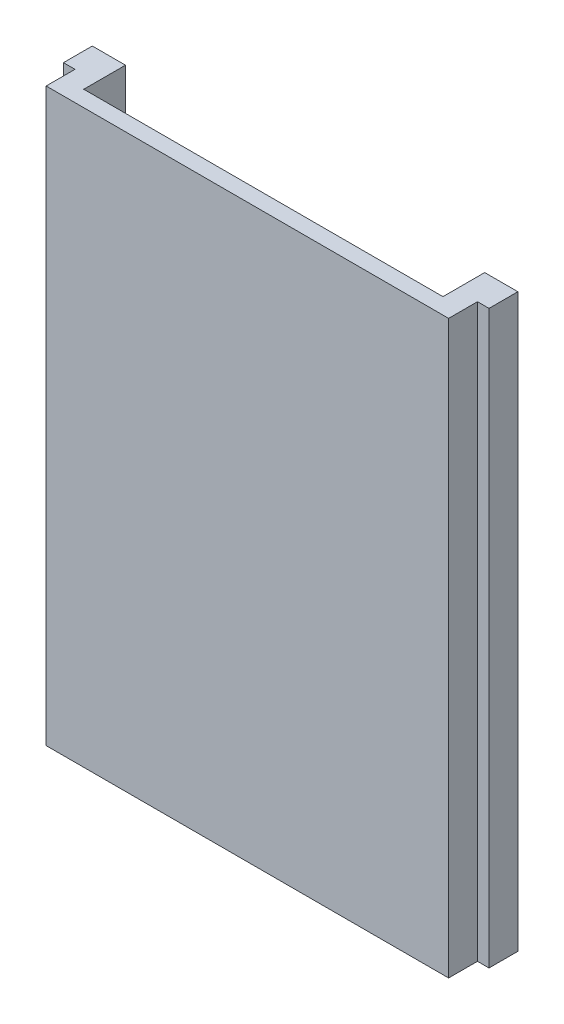
SolidWorks part; units mm, degrees
ref_plane "Alzado" through (0, 0, 0) normal (0, 0, 1) x (1, 0, 0)
ref_plane "Planta" through (0, 0, 0) normal (0, 1, 0) x (1, 0, 0)
ref_plane "Vista lateral" through (0, 0, 0) normal (1, 0, 0) x (0, 0, -1)
sketch "Croquis1" plane through (0, 0, 0) normal (0, 1, 0) x (1, 0, 0)
  line L5 (-4, 10) -> (-4, 20)
  line L11 (143.5, 20) -> (143.5, 10)
  line L14 (7.5, 20) -> (7.5, 5.5361)
  line L16 (132, 5.5361) -> (132, 20)
  line L17 (-4, 20) -> (7.5, 20)
  line L18 (132, 20) -> (143.5, 20)
  line L19 (0, 0) -> (139.5, 0)
  line L20 (0, 0) -> (0, 10)
  line L21 (0, 10) -> (-4, 10)
  line L22 (139.5, 10) -> (143.5, 10)
  line L23 (7.5, 5.5361) -> (132, 5.5361)
  line L24 (139.5, 0) -> (139.5, 10)
  dimension "D1" = 139.5
  dimension "D2" = 10
  dimension "D3" = 10
  dimension "D4" = 11.5
  dimension "D5" = 147.5
  dimension "D6" = 4
  dimension "D7" = 5.5361
extrude "Saliente-Extruir4" add sketch "Croquis1" along normal blind 198 contours L17 L14 L23 L16 L18 L11 L22 L24 L19 L20 L21 L5
